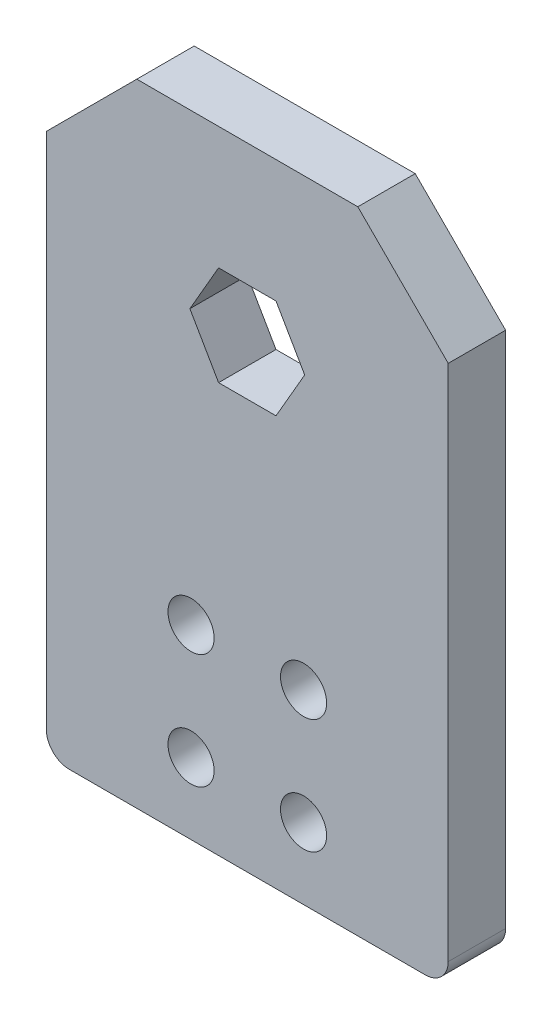
SolidWorks part; units mm, degrees
material "5052-O"
ref_plane "Front Plane" through (0, 0, 0) normal (0, 0, 1) x (1, 0, 0)
ref_plane "Top Plane" through (0, 0, 0) normal (0, 1, 0) x (1, 0, 0)
ref_plane "Right Plane" through (0, 0, 0) normal (1, 0, 0) x (0, 0, -1)
sketch "Sketch1" plane through (0, 0, 0) normal (0, 0, 1) x (1, 0, 0)
  line L1 (-22.225, -34.925) -> (22.225, -34.925)
  line L2 (-22.225, -34.925) -> (-22.225, 34.925)
  line L3 (-22.225, 34.925) -> (22.225, 34.925)
  line L4 (22.225, -34.925) -> (22.225, 34.925)
  line L5 (-22.225, -34.925) -> (22.225, 34.925) construction
  line L6 (-22.225, 34.925) -> (22.225, -34.925) construction
  point P0 (0, 0)
  dimension "D1" = 44.45
  dimension "D2" = 69.85
extrude "Boss-Extrude1" add sketch "Sketch1" along normal mid plane 6.35
chamfer "Chamfer1" distance 10 angle 45 2 edges at (22.225, 34.925, 0) (-22.225, 34.925, 0)
sketch "Sketch2" plane through (0, 0, 3.175) normal (0, 0, 1) x (1, 0, 0)
  line L1 (12.225, 34.925) -> (-12.225, 34.925) construction
  line L2 (6.35, 15.875) -> (3.175, 21.3743)
  line L3 (3.175, 21.3743) -> (-3.175, 21.3743)
  line L4 (-3.175, 21.3743) -> (-6.35, 15.875)
  line L5 (-6.35, 15.875) -> (-3.175, 10.3757)
  line L6 (-3.175, 10.3757) -> (3.175, 10.3757)
  line L7 (3.175, 10.3757) -> (6.35, 15.875)
  circle A1 centre (0, 15.875) radius 5.4993 construction
  dimension "D1" = 19.05
  dimension "D2" = 12.7
extrude "Cut-Extrude1" cut sketch "Sketch2" against normal through all
hole_wizard "Tap Drill for #10-24 Tap1" positions "Sketch4" profile "Sketch5" hole size "#10-24" standard "ANSI Inch"
sketch "Sketch4" plane through (0, -34.925, 0) normal (0, -1, 0) x (-1, 0, 0)
  line L0 (15.875, 0) -> (-15.875, 0) construction
  point P0 (15.875, 0)
  point P2 (-15.875, 0)
  point P13 (0, 0)
  dimension "D1" = 31.75
sketch "Sketch5" plane through (-15.875, -34.925, 0) normal (1, 0, 0) x (0, 0, -1)
  line L0 (0, 0) -> (0, 20.1908)
  line L1 (0, 20.1908) -> (1.8986, 19.05)
  line L2 (1.8986, 19.05) -> (1.8986, 0)
  line L5 (1.8986, 0) -> (0, 0)
  line L10 (0, 20.1908) -> (-1.8987, 19.05) construction
  line L11 (0, -6.35) -> (0, 107.95) construction
  dimension "Hole Dia." = 3.7973
  dimension "Hole Depth" = 19.05
  dimension "Drill Angle" = 118
sketch "Sketch6" plane through (0, 0, 3.175) normal (0, 0, 1) x (1, 0, 0)
  line L0 (-22.225, -34.925) -> (22.225, -34.925) construction
  line L1 (-6.223, -27.051) -> (6.223, -27.051) construction
  line L2 (-6.223, -27.051) -> (-6.223, -14.351) construction
  line L3 (-6.223, -14.351) -> (6.223, -14.351) construction
  line L4 (6.223, -27.051) -> (6.223, -14.351) construction
  line L5 (-6.223, -27.051) -> (6.223, -14.351) construction
  line L6 (-6.223, -14.351) -> (6.223, -27.051) construction
  point P0 (0, -20.701)
  dimension "D1" = 7.874
  dimension "D2" = 12.446
  dimension "D3" = 12.7
hole_wizard "#10 Clearance Hole1" positions "Sketch7" profile "Sketch8" hole size "#10" standard "ANSI Inch"
sketch "Sketch7" plane through (0, 0, 3.175) normal (0, 0, 1) x (1, 0, 0)
  point P0 (-6.223, -14.351)
  point P3 (6.223, -14.351)
  point P6 (6.223, -27.051)
  point P9 (-6.223, -27.051)
sketch "Sketch8" plane through (-6.223, -14.351, 3.175) normal (1, 0, 0) x (0, -1, 0)
  line L0 (0, 0) -> (0, 14.2338)
  line L1 (0, 14.2338) -> (2.5527, 12.7)
  line L2 (2.5527, 12.7) -> (2.5527, 0)
  line L5 (2.5527, 0) -> (0, 0)
  line L10 (0, 14.2338) -> (-2.5527, 12.7) construction
  line L11 (0, -6.35) -> (0, 107.95) construction
  dimension "Hole Dia." = 5.1054
  dimension "Hole Depth" = 12.7
  dimension "Drill Angle" = 118
fillet "Fillet1" radius 2.54 2 edges at (22.225, -34.925, 0) (-22.225, -34.925, 0)
ref_axis "Axis1" through (0, 15.875, 3.175) along (0, 0, 1)
